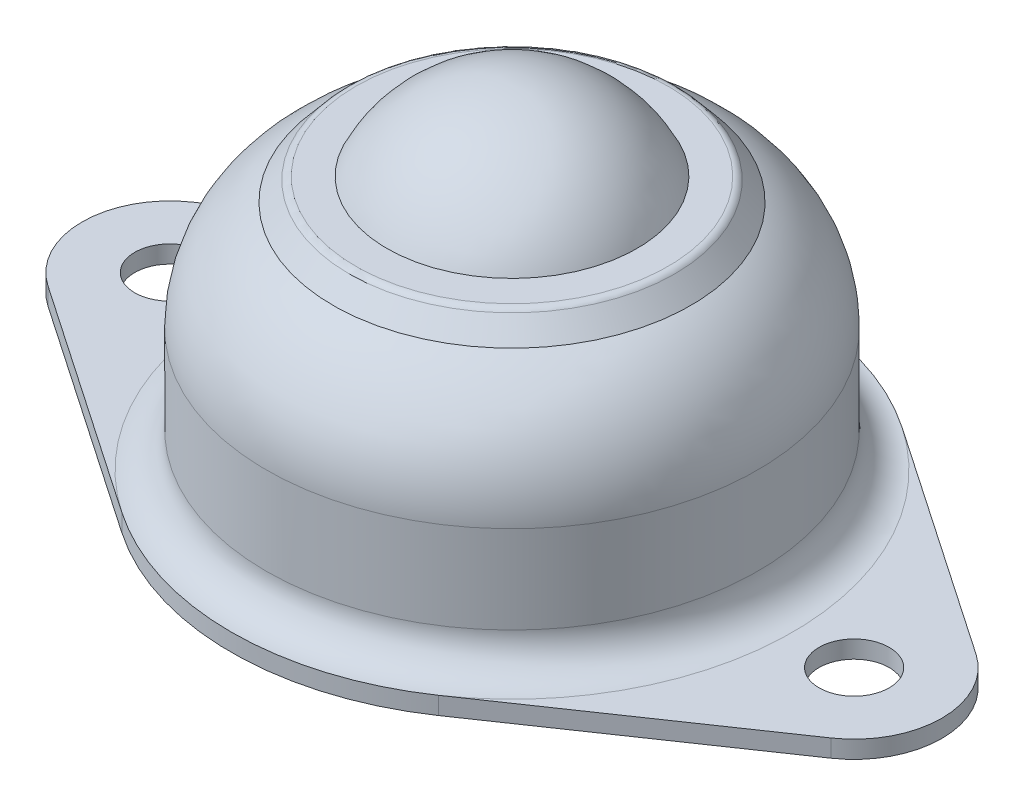
SolidWorks part; units mm, degrees
ref_plane "Front" through (0, 0, 0) normal (0, 0, 1) x (1, 0, 0)
ref_plane "Top" through (0, 0, 0) normal (0, 1, 0) x (1, 0, 0)
ref_plane "Right" through (0, 0, 0) normal (1, 0, 0) x (0, 0, -1)
sketch "草圖1" plane through (0, 0, 0) normal (0, 1, 0) x (1, 0, 0)
  line L0 (-19.5, 0) -> (19.5, 0) construction
  line L1 (-22.3205, 4.1285) -> (-9.0256, 13.2113)
  line L2 (9.0256, 13.2113) -> (22.3205, 4.1285)
  line L3 (-22.3205, -4.1285) -> (-9.0256, -13.2113)
  line L4 (9.0256, -13.2113) -> (22.3205, -4.1285)
  line L5 (0, -16) -> (0, 16) construction
  circle A0 centre (19.5, 0) radius 2
  circle A1 centre (-19.5, 0) radius 2
  arc A3 (-22.3205, 4.1285) -> (-22.3205, -4.1285) centre (-19.5, 0) ccw
  arc A4 (22.3205, -4.1285) -> (22.3205, 4.1285) centre (19.5, 0) ccw
  arc A5 (-9.0256, -13.2113) -> (9.0256, -13.2113) centre (0, 0) ccw
  arc A8 (9.0256, 13.2113) -> (-9.0256, 13.2113) centre (0, 0) ccw
  dimension "D1" = 4
  dimension "D2" = 4
  dimension "D4" = 16
  dimension "D5" = 10
  dimension "D6" = 10
  dimension "D7" = 16
  dimension "D3" = 39
extrude "填料-伸長1" add sketch "草圖1" along normal blind 1
sketch "草圖2" plane through (0, 0, 0) normal (0, 0, 1) x (1, 0, 0)
  line L0 (-14, 1) -> (-14, 8)
  line L1 (-22.3205, 1) -> (-9.0256, 1) construction
  line L3 (0, 20) -> (0, 1)
  line L4 (9.0256, 1) -> (-9.0256, 1) construction
  line L5 (0, 1) -> (-14, 1)
  line L6 (-7.1309, 15.5) -> (-8.8978, 15.5)
  line L7 (-9.2808, 15.3214) -> (-10.2002, 14.2256)
  arc A1 (-7.1309, 15.5) -> (0, 20) centre (0, 12.1) cw
  arc A3 (-14, 8) -> (-10.2002, 14.2256) centre (-7, 8) cw
  arc A4 (-8.8978, 15.5) -> (-9.2808, 15.3214) centre (-8.8978, 15) ccw
  point P14 (-9.1309, 15.5)
  dimension "D1" = 7.9
  dimension "D4" = 4.5
  dimension "D5" = 7
  dimension "D7" = 130
  dimension "D8" = 7
  dimension "D9" = 0.5
  dimension "D2" = 19
  dimension "D3" = 14
  dimension "D6" = 2
  dimension "D10" = 11.1
revolve "旋轉1" add sketch "草圖2" angle 360 about L3
fillet "圓角1" radius 2 1 edges at (0, 1, 14)
sketch "草圖3" plane through (0, 0, 0) normal (0, 0, 1) x (1, 0, 0)
  line L3 (0, 0) -> (-13, 0)
  line L6 (-22.3205, 0) -> (-9.0256, 0) construction
  line L7 (-13, 0) -> (-13, 7)
  line L11 (-13, 7) -> (-12.7, 7)
  line L13 (-9.0256, 1) -> (9.0256, 1) construction
  line L14 (0, 1) -> (0, 0)
  spline S0 degree 2 poles (-12.7, 7) (-8.5987, 1) (0, 1) knots 0 0 0 1 1 1
  dimension "D2" = 13
  dimension "D3" = 7
  dimension "D4" = 0.3
revolve "除料-旋轉1" cut sketch "草圖3" angle 360 about L14
fillet "圓角3" radius 2 1 edges at (-13, 0, 0)
